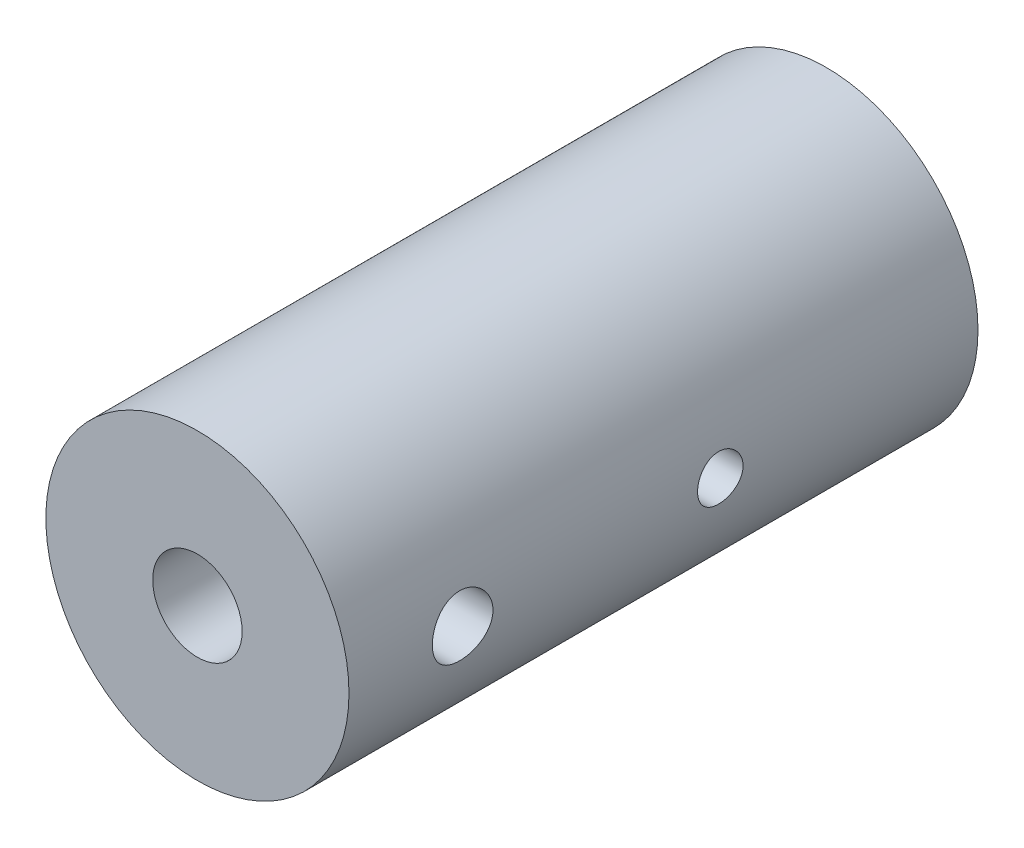
SolidWorks part; units mm, degrees
ref_plane "Front Plane" through (0, 0, 0) normal (0, 0, 1) x (1, 0, 0)
ref_plane "Top Plane" through (0, 0, 0) normal (0, 1, 0) x (1, 0, 0)
ref_plane "Right Plane" through (0, 0, 0) normal (1, 0, 0) x (0, 0, -1)
sketch "Sketch1" plane through (0, 0, 0) normal (0, 0, 1) x (1, 0, 0)
  circle A0 centre (0, 0) radius 10
  dimension "D1" = 20
extrude "Boss-Extrude1" add sketch "Sketch1" along normal blind 41.5
sketch "Sketch2" plane through (0, 0, 41.5) normal (0, 0, 1) x (1, 0, 0)
  circle A0 centre (0, 0) radius 2.95
  dimension "D1" = 5.9
extrude "Cut-Extrude1" cut sketch "Sketch2" against normal blind 15
sketch "Sketch3" plane through (0, 0, 0) normal (0, 0, -1) x (-1, 0, 0)
  circle A0 centre (0, 0) radius 6
  dimension "D1" = 12
extrude "Cut-Extrude2" cut sketch "Sketch3" against normal blind 22
ref_plane "Plane1" through (-10, 0, 0) normal (-1, 0, 0) x (0, 0, 1)
sketch "Sketch4" plane through (-10, 0, 0) normal (-1, 0, 0) x (0, 0, 1)
  line L0 (0, 10) -> (0, -10) construction
  line L1 (41.5, -10) -> (41.5, 10) construction
  circle A0 centre (17, 0) radius 1.5
  circle A1 centre (34, 0) radius 2
  dimension "D3" = 3
  dimension "D4" = 4
  dimension "D1" = 17
  dimension "D2" = 7.5
extrude "Cut-Extrude3" cut sketch "Sketch4" against normal up to next
ref_plane "Plane2" through (10, 0, 0) normal (1, 0, 0) x (0, 0, -1)
extrude "Cut-Extrude4" cut sketch "Sketch4<2>" along normal up to next from surface starting at plane "Plane2"
sketch "Sketch4<2>" plane through (-10, 0, 0) normal (-1, 0, 0) x (0, 0, 1) same geometry as "Sketch4"
